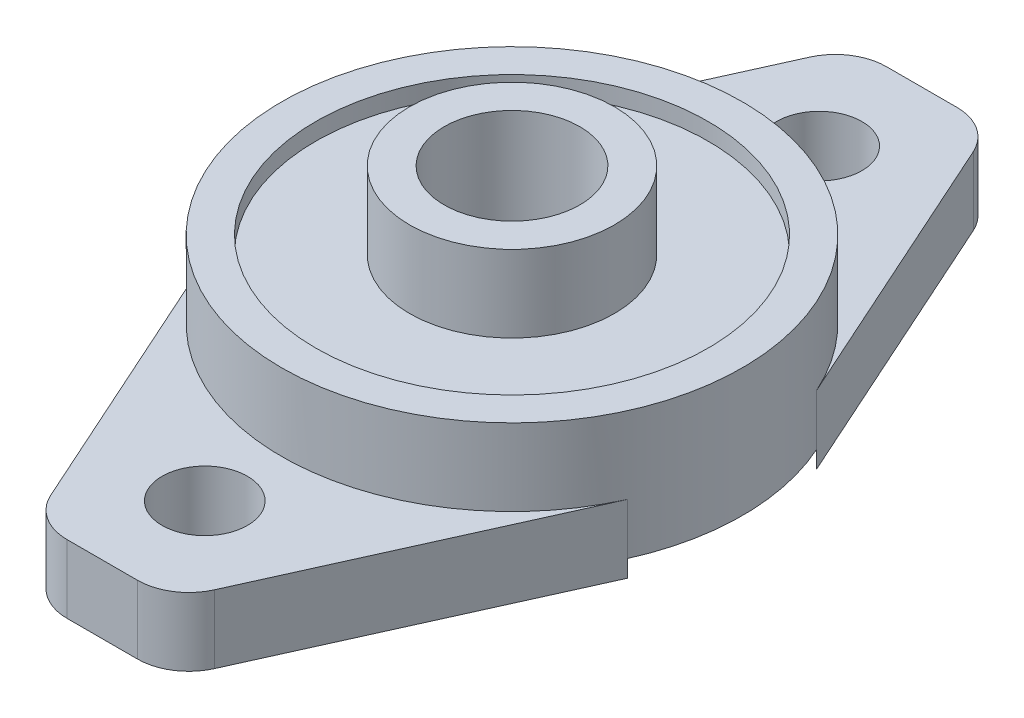
SolidWorks part; units mm, degrees
ref_plane "前视基准面" through (0, 0, 0) normal (0, 0, 1) x (1, 0, 0)
ref_plane "上视基准面" through (0, 0, 0) normal (0, 1, 0) x (1, 0, 0)
ref_plane "右视基准面" through (0, 0, 0) normal (1, 0, 0) x (0, 0, -1)
other "Configuration Table"
sketch "草图1" plane through (0, 0, 0) normal (0, 1, 0) x (1, 0, 0)
  line L0 (0, 0) -> (0, 24) construction
  line L1 (0, 0) -> (0, -24) construction
  line L2 (-13.5, 0) -> (13.5, 0) construction
  line L3 (-4, 24) -> (4, 24)
  line L4 (-4, 24) -> (-12.31, 5.5421)
  line L5 (4, 24) -> (12.31, 5.5421)
  line L6 (4, -24) -> (12.31, -5.5421)
  line L7 (-4, -24) -> (4, -24)
  line L8 (-4, -24) -> (-12.31, -5.5421)
  circle A0 centre (0, 0) radius 13.5
  circle A1 centre (0, 0) radius 4
  circle A2 centre (0, 18) radius 2.5
  circle A3 centre (0, -18) radius 2.5
  dimension "D1" = 27
  dimension "D2" = 8
  dimension "D5" = 5
  dimension "D3" = 24
  dimension "D4" = 24
  dimension "D6" = 18
  dimension "D7" = 8
extrude "凸台-拉伸1" add sketch "草图1" along normal blind 4 contours A0 L5 L3 L4 A2 | A0 A1 | A0 L8 L7 L6 A3 region at (0, 0, -23.6923) region at (0, 0, -13.1182) region at (0, 0, 13.8077)
extrude "凸台-拉伸2" add sketch "草图1<3>" along normal blind 8.5 contours A0 A1 region at (0, 0, -13.1182)
sketch "草图1<3>" plane through (0, 0, 0) normal (0, 1, 0) x (1, 0, 0) same geometry as "草图1"
extrude "切除-拉伸1" cut sketch "草图1<5>" along normal blind 1 contours A0 A1 region at (0, 0, -13.1182)
sketch "草图1<5>" plane through (0, 0, 0) normal (0, 1, 0) x (1, 0, 0) same geometry as "草图1"
sketch "草图2" plane through (0, 1, 0) normal (0, -1, 0) x (1, 0, 0)
  circle A0 centre (0, 0) radius 6
  circle A1 centre (0, 0) radius 3.975
  dimension "D1" = 12
extrude "凸台-拉伸4" add sketch "草图2" along normal blind 1 and the other way blind 11
sketch "草图3" plane through (0, 8.5, 0) normal (0, 1, 0) x (1, 0, 0)
  circle A0 centre (0, 0) radius 6
  circle A1 centre (0, 0) radius 11.5
  dimension "D1" = 12
  dimension "D2" = 23
extrude "切除-拉伸2" cut sketch "草图3" against normal blind 1
fillet "圆角1" radius 3 4 edges at (4, 2, 24) (-4, 2, 24) (4, 2, -24) (-4, 2, -24)
extrude "切除-拉伸3" cut sketch "草图3<2>" along normal blind 1 from surface starting at face at (0, 1, 6)
sketch "草图3<2>" plane through (0, 8.5, 0) normal (0, 1, 0) x (1, 0, 0) same geometry as "草图3"
